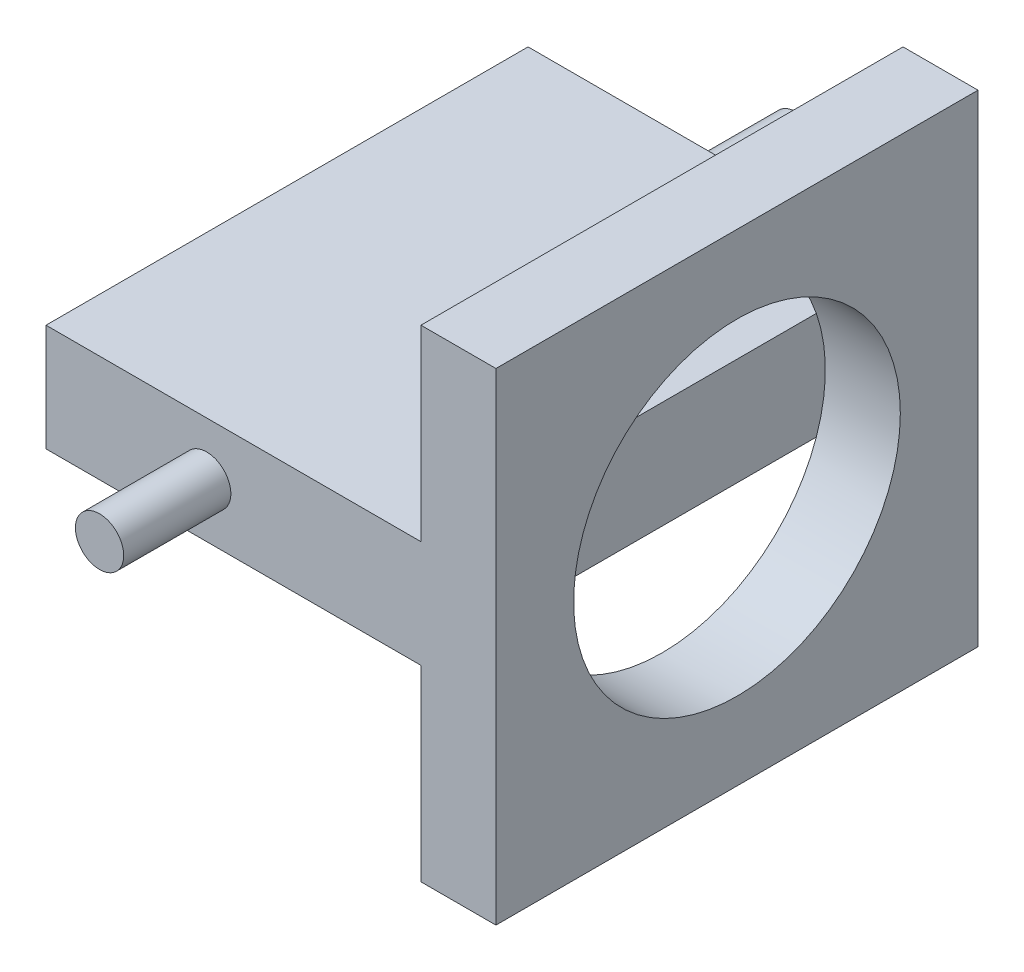
SolidWorks part; units mm, degrees
ref_plane "Front Plane" through (0, 0, 0) normal (0, 0, 1) x (1, 0, 0)
ref_plane "Top Plane" through (0, 0, 0) normal (0, 1, 0) x (1, 0, 0)
ref_plane "Right Plane" through (0, 0, 0) normal (1, 0, 0) x (0, 0, -1)
sketch "Sketch1" plane through (0, 0, 0) normal (1, 0, 0) x (0, 0, -1)
  line L1 (-22.5, -22.5) -> (22.5, -22.5)
  line L2 (-22.5, -22.5) -> (-22.5, 22.5)
  line L3 (-22.5, 22.5) -> (22.5, 22.5)
  line L4 (22.5, -22.5) -> (22.5, 22.5)
  line L5 (-22.5, -22.5) -> (22.5, 22.5) construction
  line L6 (-22.5, 22.5) -> (22.5, -22.5) construction
  circle A0 centre (0, 0) radius 15.25
  dimension "D1" = 30.5
  dimension "D2" = 45
  dimension "D3" = 45
extrude "Boss-Extrude1" add sketch "Sketch1" along normal blind 7
sketch "Sketch2" plane through (0, 0, 0) normal (-1, 0, 0) x (0, 0, 1)
  line L0 (22.5, 22.5) -> (22.5, -22.5) construction
  line L1 (-22.5, -5) -> (22.5, -5)
  line L2 (-22.5, -5) -> (-22.5, 5)
  line L3 (-22.5, 5) -> (22.5, 5)
  line L4 (22.5, -5) -> (22.5, 5)
  line L5 (-22.5, -5) -> (22.5, 5) construction
  line L6 (-22.5, 5) -> (22.5, -5) construction
  point P0 (0, 0)
  dimension "D1" = 10
extrude "Boss-Extrude2" add sketch "Sketch2" along normal blind 35
sketch "Sketch3" plane through (0, 0, 22.5) normal (0, 0, 1) x (1, 0, 0)
  line L0 (-35, -5) -> (-35, 5) construction
  circle A0 centre (-20, 0) radius 2.2544
  dimension "D1" = 15
extrude "Boss-Extrude3" add sketch "Sketch3" along normal blind 10
mirror "Mirror1" about plane through (0, 0, 0) normal (0, 0, 1) of "Boss-Extrude3"
